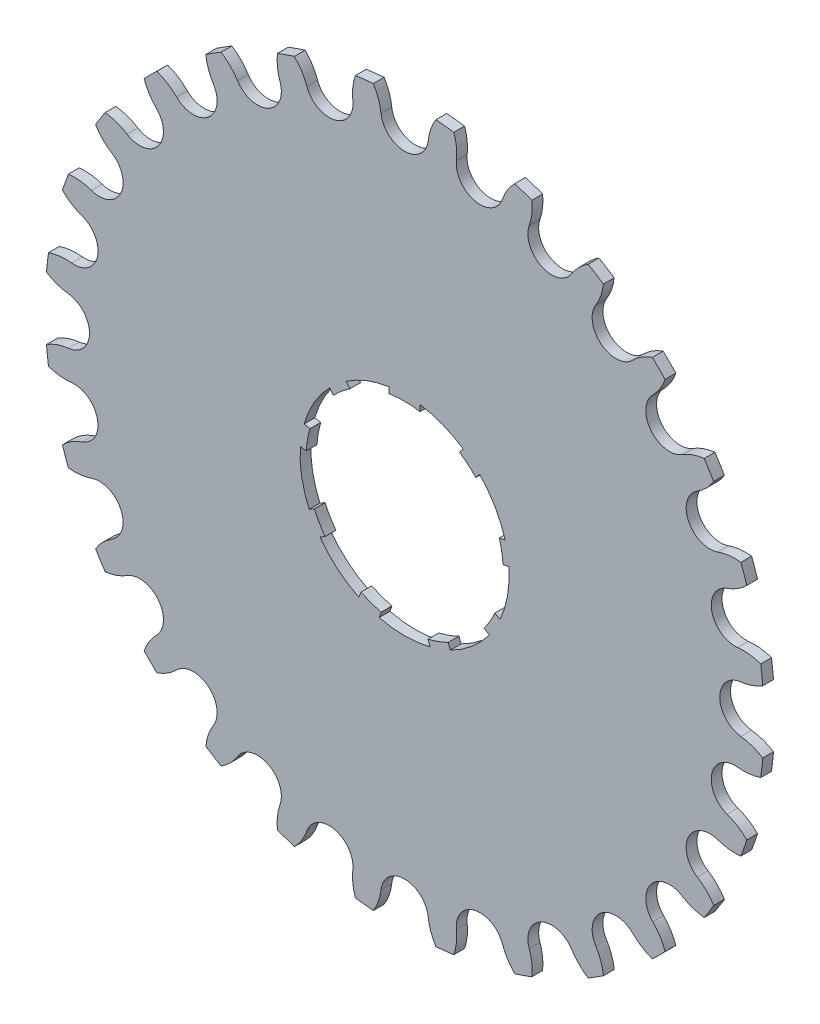
SolidWorks part; units mm, degrees
ref_plane "Alzado" through (0, 0, 0) normal (0, 0, 1) x (1, 0, 0)
ref_plane "Planta" through (0, 0, 0) normal (0, 1, 0) x (1, 0, 0)
ref_plane "Vista lateral" through (0, 0, 0) normal (1, 0, 0) x (0, 0, -1)
sketch "Sk_Disco" plane through (0, 0, 0) normal (0, 0, 1) x (1, 0, 0)
  line L0 (2.6, 17.3058) -> (2.6, 16.2939)
  line L1 (-2.6, 16.2939) -> (-2.6, 17.3058)
  line L2 (-9.8102, 14.4917) -> (-9.1638, 13.7213)
  line L3 (-11.9216, 11.4073) -> (-12.568, 12.1777)
  line L4 (-16.8302, 4.7954) -> (-15.8398, 4.6207)
  line L5 (-16.4649, 1.0754) -> (-17.4553, 1.2501)
  line L6 (-15.9751, -7.1447) -> (-15.1041, -6.6419)
  line L7 (-13.3041, -9.7596) -> (-14.1751, -10.2624)
  line L8 (-7.6451, -15.7418) -> (-7.3011, -14.7968)
  line L9 (-3.9182, -16.028) -> (-4.2622, -16.973)
  line L10 (4.2622, -16.973) -> (3.9182, -16.028)
  line L11 (7.3011, -14.7968) -> (7.6451, -15.7418)
  line L12 (14.1751, -10.2624) -> (13.3041, -9.7596)
  line L13 (15.1041, -6.6419) -> (15.9751, -7.1447)
  line L14 (17.4553, 1.2501) -> (16.4649, 1.0754)
  line L15 (15.8398, 4.6207) -> (16.8302, 4.7954)
  line L16 (12.568, 12.1777) -> (11.9216, 11.4073)
  line L17 (9.1638, 13.7213) -> (9.8102, 14.4917)
  circle A0 centre (0, 0) radius 60.1678
  arc A1 (2.6, 16.2939) -> (-2.6, 16.2939) centre (0, 0) ccw
  arc A2 (-2.6, 17.3058) -> (-9.8102, 14.4917) centre (0, 0) ccw
  arc A3 (-9.1638, 13.7213) -> (-11.9216, 11.4073) centre (0, 0) ccw
  arc A4 (-12.568, 12.1777) -> (-16.8302, 4.7954) centre (0, 0) ccw
  arc A5 (-15.8398, 4.6207) -> (-16.4649, 1.0754) centre (0, 0) ccw
  arc A6 (-17.4553, 1.2501) -> (-15.9751, -7.1447) centre (0, 0) ccw
  arc A7 (-15.1041, -6.6419) -> (-13.3041, -9.7596) centre (0, 0) ccw
  arc A8 (-14.1751, -10.2624) -> (-7.6451, -15.7418) centre (0, 0) ccw
  arc A9 (-7.3011, -14.7968) -> (-3.9182, -16.028) centre (0, 0) ccw
  arc A10 (-4.2622, -16.973) -> (4.2622, -16.973) centre (0, 0) ccw
  arc A11 (3.9182, -16.028) -> (7.3011, -14.7968) centre (0, 0) ccw
  arc A12 (7.6451, -15.7418) -> (14.1751, -10.2624) centre (0, 0) ccw
  arc A13 (13.3041, -9.7596) -> (15.1041, -6.6419) centre (0, 0) ccw
  arc A14 (15.9751, -7.1447) -> (17.4553, 1.2501) centre (0, 0) ccw
  arc A15 (16.4649, 1.0754) -> (15.8398, 4.6207) centre (0, 0) ccw
  arc A16 (16.8302, 4.7954) -> (12.568, 12.1777) centre (0, 0) ccw
  arc A17 (11.9216, 11.4073) -> (9.1638, 13.7213) centre (0, 0) ccw
  arc A18 (9.8102, 14.4917) -> (2.6, 17.3058) centre (0, 0) ccw
  dimension "D1" = 120.3356
extrude "Disco" add sketch "Sk_Disco" along normal blind 1.8
sketch "Sk_Hueco" plane through (0, 0, 0) normal (0, 0, 1) x (1, 0, 0)
  line L0 (0, 0) -> (0, 56.7144) construction
  line L1 (0, 0) -> (-12.6201, 55.2925) construction
  line L2 (0, 0) -> (12.6201, 55.2925) construction
  line L3 (0, 56.7144) -> (-12.6201, 55.2925) construction
  line L4 (0, 56.7144) -> (12.6201, 55.2925) construction
  arc A0 (-3.95, 56.2694) -> (3.95, 56.2694) centre (0, 56.7144) ccw
  arc A1 (-3.95, 56.2694) -> (-6.8022, 61.7946) centre (-12.6201, 55.2925) ccw
  arc A2 (6.8022, 61.7946) -> (3.95, 56.2694) centre (12.6201, 55.2925) ccw
  arc A3 (6.8022, 61.7946) -> (-6.8022, 61.7946) centre (0, 0) ccw
  dimension "D6" = 3.975
  dimension "D7" = 62.1678
  dimension "D1" = 56.7144
  dimension "D2" = 56.7144
  dimension "D3" = 56.7144
  dimension "D4" = 12.857
  dimension "D5" = 12.857
extrude "Hueco_diente" cut sketch "Sk_Hueco" along normal through all
ref_axis "Eje_pinon" through (0, 0, -0.09) along (0, 0, 1)
pattern_circular "Matriz_dientes" count 28 over 360 about axis through (0, 0, -0.09) along (0, 0, 1) of "Hueco_diente"
equation "\"Z\"= 28"
equation "\"p\"= 12.7"
equation "\"Dr\"= 7.75"
equation "\"e\"= 1.8"
equation "\"D\"= \"p\" / sin ( 180 / \"Z\" )"
equation "\"De\"= \"p\" * ( 0.6 + 1 / tan ( 180 / \"Z\" ) )"
equation "\"Di\"= \"D\" - \"Dr\""
equation "\"Ang\"= 360 / \"Z\""
equation "\"D1@Sk_Disco\" = \"De\""
equation "\"D1@Disco\" = \"e\""
equation "\"D1@Sk_Hueco\" = \"D\" / 2"
equation "\"D2@Sk_Hueco\" = \"D\" / 2"
equation "\"D3@Sk_Hueco\" = \"D\" / 2"
equation "\"D4@Sk_Hueco\" = \"Ang\""
equation "\"D5@Sk_Hueco\" = \"Ang\""
equation "\"D6@Sk_Hueco\" = \"Dr\" / 2 + 0.1"
equation "\"D7@Sk_Hueco\" = \"De\" / 2 + 2"
equation "\"D1@Matriz_dientes\" = \"Z\""
